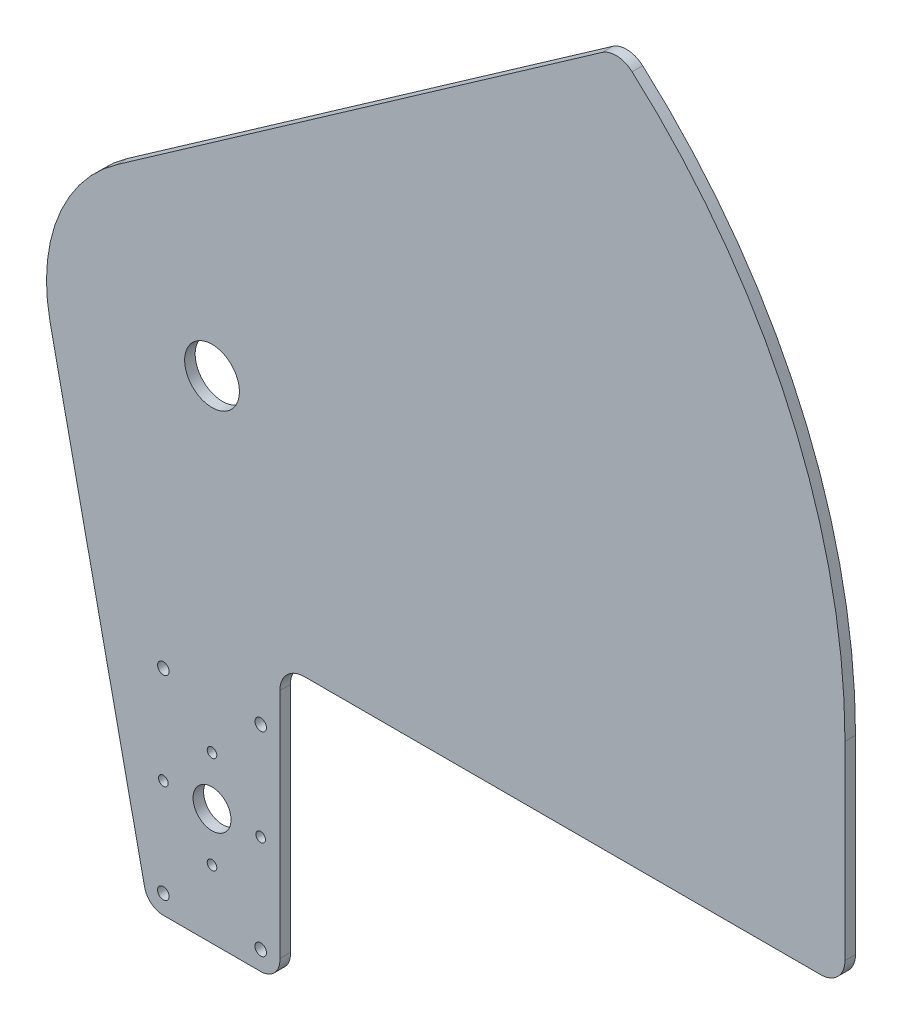
SolidWorks part; units mm, degrees
note: The reader was unsure of these and kept them because the rebuilt part matched: shared geometry of "Sketch4<3>".
ref_plane "Front Plane" through (0, 0, 0) normal (0, 0, 1) x (1, 0, 0)
ref_plane "Top Plane" through (0, 0, 0) normal (0, 1, 0) x (1, 0, 0)
ref_plane "Right Plane" through (0, 0, 0) normal (1, 0, 0) x (0, 0, -1)
sketch "Sketch1" plane through (0, 0, 0) normal (0, 0, 1) x (1, 0, 0)
  line L0 (0, -86.36) -> (0, -111.76) construction
  line L1 (0, -111.76) -> (330.2, -111.76)
  line L2 (330.2, -111.76) -> (330.2, 0)
  line L3 (-49.5341, 70.742) -> (211.5352, 253.5447)
  line L4 (0, -111.76) -> (0, -86.36)
  circle A0 centre (0, 0) radius 14.2875
  circle A1 centre (0, 0) radius 33.401 construction
  circle A2 centre (0, 0) radius 76.2 construction
  circle A4 centre (0, 0) radius 86.36
  circle A5 centre (190.5, 0) radius 114.3 construction
  arc A6 (283.5714, -111.76) -> (189.9121, 238.404) centre (0, 0) ccw construction
  arc A7 (310.7117, -111.76) -> (211.5352, 253.5447) centre (0, 0) ccw
  arc A8 (297.18, -111.76) -> (200.741, 245.9864) centre (0, 0) ccw construction
  arc A9 (211.5352, 253.5447) -> (310.7117, -111.76) centre (0, 0) ccw construction
  circle A10 centre (0, 0) radius 330.2 construction
  arc A11 (200.741, 245.9864) -> (297.18, -111.76) centre (0, 0) ccw construction
  circle A12 centre (0, 0) radius 317.5 construction
  arc A13 (189.9121, 238.404) -> (283.5714, -111.76) centre (0, 0) ccw construction
  circle A14 centre (0, 0) radius 304.8 construction
  dimension "D1" = 28.575
  dimension "D2" = 66.802
  dimension "D3" = 152.4
  dimension "D4" = 10.16
  dimension "D5" = 228.6
  dimension "D6" = 12.7
  dimension "D8" = 25.4
  dimension "D9" = 35
  dimension "D7" = 12.7
extrude "Boss-Extrude1" add sketch "Sketch1" along normal mid plane 5.5 contours A4 A0 | A7 L3 A4 L4 L1 | A7 L1 L2
sketch "Sketch2" plane through (0, 0, 2.75) normal (0, 0, 1) x (1, 0, 0)
  line L0 (0, 0) -> (0, -195.58) construction
  line L2 (33.4, -195.58) -> (33.4, -111.76)
  line L3 (-32.1522, -204.6242) -> (-83.1336, -23.3849)
  line L4 (0, -111.76) -> (330.2, -111.76) construction
  circle A0 centre (0, -195.58) radius 9.906
  circle A1 centre (0, -195.58) radius 25.4 construction
  circle A2 centre (0, -170.18) radius 2.5
  circle A3 centre (25.4, -195.58) radius 2.5
  circle A4 centre (0, -220.98) radius 2.5
  circle A5 centre (-25.4, -195.58) radius 2.5
  circle A6 centre (0, -195.58) radius 33.4
  arc A7 (-49.5341, 70.742) -> (0, -86.36) centre (0, 0) ccw construction
  point P18 (0, -195.58)
  dimension "D3" = 19.812
  dimension "D4" = 50.8
  dimension "D5" = 5
  dimension "D1" = 195.58
  dimension "D7" = 8
  dimension "D6" = 4
extrude "Boss-Extrude2" add sketch "Sketch2" against normal up to surface (5.5 mm away)
fillet "Fillet2" radius 12.7 3 edges at (330.2, -111.76, 0) (211.5352, 253.5447, 0) (33.4, -111.76, 0)
sketch "Sketch4" plane through (0, 0, 2.75) normal (0, 0, 1) x (1, 0, 0)
  line L0 (0, 0) -> (0, -195.58) construction
  line L1 (0, -195.58) -> (-25.4, -195.58) construction
  line L2 (-84.4507, -18.0591) -> (-35.1789, -248.4711)
  line L3 (-25.4, -256.38) -> (25.4, -256.38)
  line L4 (35.369, -245.5938) -> (35.369, -117.6676)
  line L10 (46.1, -111.76) -> (317.5, -111.76)
  line L11 (330.2, -99.06) -> (330.2, 0)
  line L12 (203.4506, 247.8837) -> (-49.5341, 70.742)
  line L13 (-83.1336, -23.3849) -> (-32.1522, -204.6242)
  line L14 (33.4, -195.58) -> (33.4, -124.46)
  line L15 (46.1, -111.76) -> (317.5, -111.76)
  line L16 (330.2, -99.06) -> (330.2, 0)
  line L17 (203.4506, 247.8837) -> (-49.5341, 70.742)
  line L18 (-83.1336, -23.3849) -> (-32.1522, -204.6242)
  line L19 (33.4, -195.58) -> (33.4, -124.46)
  circle A0 centre (-25.4, -144.78) radius 3
  circle A1 centre (25.4, -144.78) radius 3
  circle A2 centre (-25.4, -246.38) radius 3
  circle A3 centre (25.4, -246.38) radius 3
  arc A4 (-25.4, -256.38) -> (-35.1789, -248.4711) centre (-25.4, -246.38) cw
  arc A5 (25.4, -256.38) -> (35.369, -245.5938) centre (25.4, -246.38) ccw
  arc A6 (-32.1522, -204.6242) -> (33.4, -195.58) centre (0, -195.58) ccw construction
  arc A7 (-32.1522, -204.6242) -> (33.4, -195.58) centre (0, -195.58) ccw
  arc A8 (-35.1789, -248.4711) -> (-25.4, -256.38) centre (-25.4, -246.38) cw construction
  circle A9 centre (-25.4, -246.38) radius 10 construction
  arc A10 (35.369, -245.5938) -> (25.4, -256.38) centre (25.4, -246.38) ccw construction
  circle A11 centre (25.4, -246.38) radius 10 construction
  arc A12 (-49.5341, 70.742) -> (-83.1336, -23.3849) centre (0, 0) ccw construction
  arc A19 (317.5, -111.76) -> (330.2, -99.06) centre (317.5, -99.06) ccw
  arc A20 (330.2, 0) -> (219.1644, 246.9797) centre (0, 0) ccw
  arc A21 (219.1644, 246.9797) -> (203.4506, 247.8837) centre (210.735, 237.4805) ccw
  arc A22 (-49.5341, 70.742) -> (-83.1336, -23.3849) centre (0, 0) ccw
  arc A23 (-32.1522, -204.6242) -> (33.4, -195.58) centre (0, -195.58) ccw
  arc A24 (46.1, -111.76) -> (33.4, -124.46) centre (46.1, -124.46) ccw
  arc A25 (317.5, -111.76) -> (330.2, -99.06) centre (317.5, -99.06) ccw
  arc A26 (330.2, 0) -> (219.1644, 246.9797) centre (0, 0) ccw
  arc A27 (219.1644, 246.9797) -> (203.4506, 247.8837) centre (210.735, 237.4805) ccw
  arc A28 (-49.5341, 70.742) -> (-83.1336, -23.3849) centre (0, 0) ccw
  arc A29 (-32.1522, -204.6242) -> (33.4, -195.58) centre (0, -195.58) ccw
  arc A30 (46.1, -111.76) -> (33.4, -124.46) centre (46.1, -124.46) ccw
  dimension "D3" = 6
  dimension "D1" = 25.4
  dimension "D2" = 50.8
  dimension "D4" = 7
  dimension "D5" = 0
extrude "Boss-Extrude3" add sketch "Sketch4" against normal up to surface (5.5 mm away)
extrude "Cut-Extrude1" cut sketch "Sketch4<3>" against normal through all both and the other way through all contours A0 | A1
sketch "Sketch4<3>" plane through (0, 0, 2.75) normal (0, 0, 1) x (1, 0, 0) same geometry as "Sketch4"
fillet "Fillet3" radius 12.7 1 edges at (35.369, -117.6676, 0)
